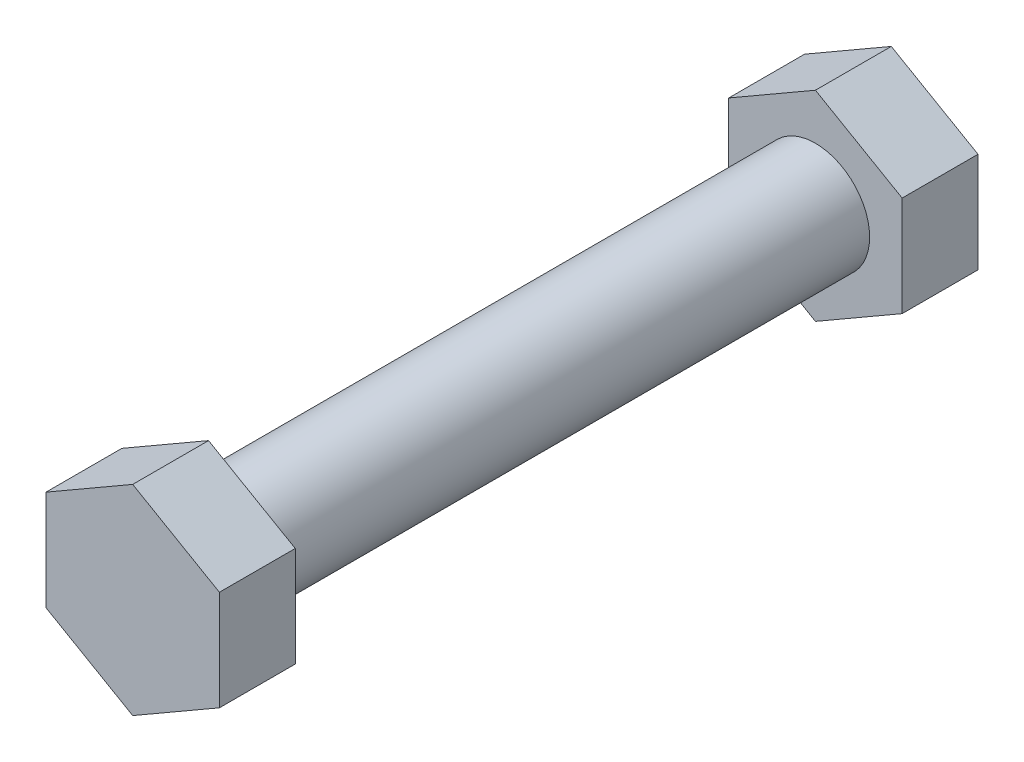
SolidWorks part; units mm, degrees
material "AISI 316 Annealed Stainless Steel Bar (SS)"
ref_plane "Front Plane" through (0, 0, 0) normal (0, 0, 1) x (1, 0, 0)
ref_plane "Top Plane" through (0, 0, 0) normal (0, 1, 0) x (1, 0, 0)
ref_plane "Right Plane" through (0, 0, 0) normal (1, 0, 0) x (0, 0, -1)
sketch "Extrude sketch 1" plane through (0, 0, 0) normal (0, 0, 1) x (1, 0, 0)
  circle A0 centre (0, 0) radius 5
  dimension "D1" = 10
extrude "Extrude 1" add sketch "Extrude sketch 1" along normal blind 66 from offset 33 separate body offset against normal yes
sketch "Extrude sketch 2" plane through (0, 0, 0) normal (0, 0, 1) x (1, 0, 0)
  line L0 (8, 4.6188) -> (0, 9.2376)
  line L1 (0, 9.2376) -> (-8, 4.6188)
  line L2 (-8, 4.6188) -> (-8, -4.6188)
  line L3 (-8, -4.6188) -> (0, -9.2376)
  line L4 (0, -9.2376) -> (8, -4.6188)
  line L5 (8, -4.6188) -> (8, 4.6188)
  dimension "D1" = 8
  dimension "D2" = 4.6188
extrude "Extrude 2" add sketch "Extrude sketch 2" along normal blind 7 from offset 28 separate body
sketch "Extrude sketch 3" plane through (0, 0, 0) normal (0, 0, 1) x (1, 0, 0)
  line L0 (8, 4.6188) -> (0, 9.2376)
  line L1 (0, 9.2376) -> (-8, 4.6188)
  line L2 (-8, 4.6188) -> (-8, -4.6188)
  line L3 (-8, -4.6188) -> (0, -9.2376)
  line L4 (0, -9.2376) -> (8, -4.6188)
  line L5 (8, -4.6188) -> (8, 4.6188)
  dimension "D1" = 8
  dimension "D2" = 4.6188
extrude "Extrude 3" add sketch "Extrude sketch 3" along normal blind 7 from offset 35 separate body offset against normal yes
combine bodies "Combine (weld / assembly of features)" operation type add bodies to combine 103 102 101
